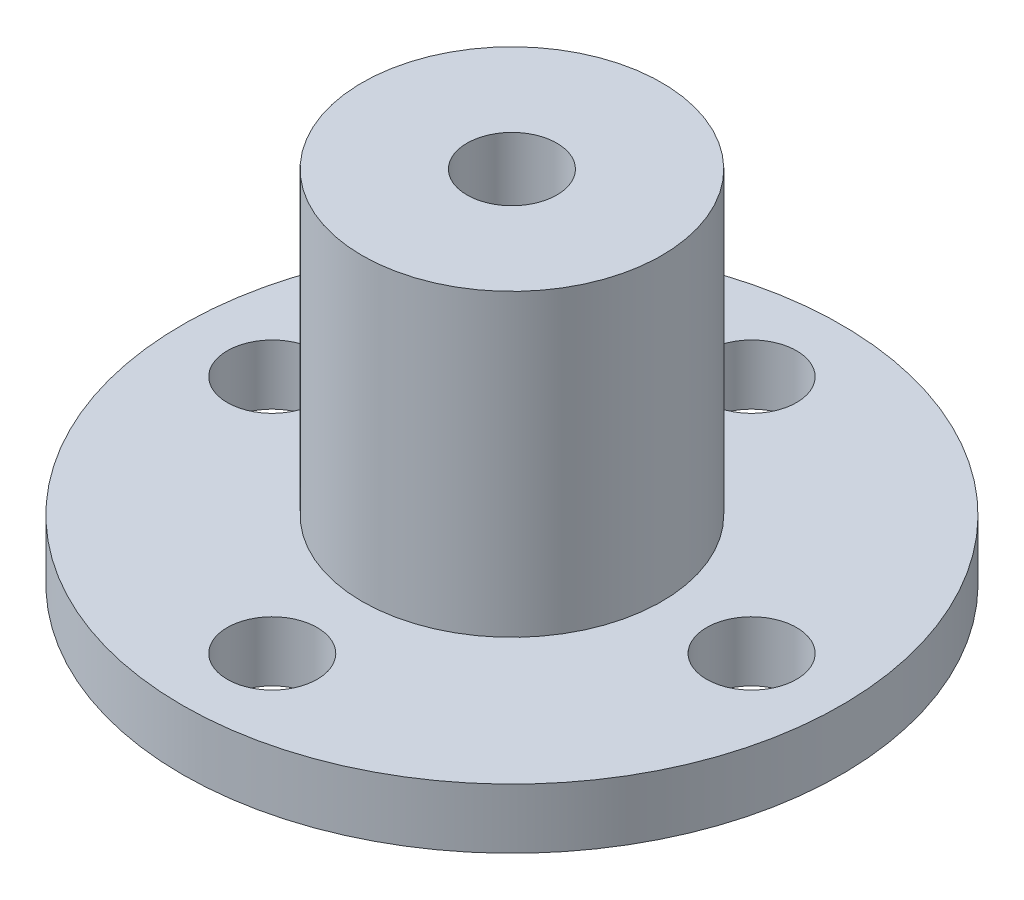
SolidWorks part; units mm, degrees
ref_plane "Front Plane" through (0, 0, 0) normal (0, 0, 1) x (1, 0, 0)
ref_plane "Top Plane" through (0, 0, 0) normal (0, 1, 0) x (1, 0, 0)
ref_plane "Right Plane" through (0, 0, 0) normal (1, 0, 0) x (0, 0, -1)
sketch "Sketch1" plane through (0, 0, 0) normal (0, 1, 0) x (1, 0, 0)
  line L0 (5, 0) -> (11, 0)
  circle A0 centre (0, 0) radius 11
  circle A1 centre (0, 0) radius 5
  circle A3 centre (8, 0) radius 1.5
  circle A4 centre (0, -8) radius 1.5
  circle A5 centre (-8, 0) radius 1.5
  circle A6 centre (0, 8) radius 1.5
  dimension "D1" = 4
extrude "Boss-Extrude1" add sketch "Sketch1" along normal blind 2 contours A3 A0 A1 A6 A5 A4 region at (-10.6889, 0, 0)
extrude "Boss-Extrude2" add sketch "Sketch1<3>" along normal blind 12 contours A1 region at (0, 0, 0)
sketch "Sketch1<3>" plane through (0, 0, 0) normal (0, 1, 0) x (1, 0, 0) same geometry as "Sketch1"
sketch "Sketch2" plane through (0, 12, 0) normal (0, 1, 0) x (1, 0, 0)
  circle A0 centre (0, 0) radius 1.5
extrude "Cut-Extrude1" cut sketch "Sketch2" against normal blind 10
